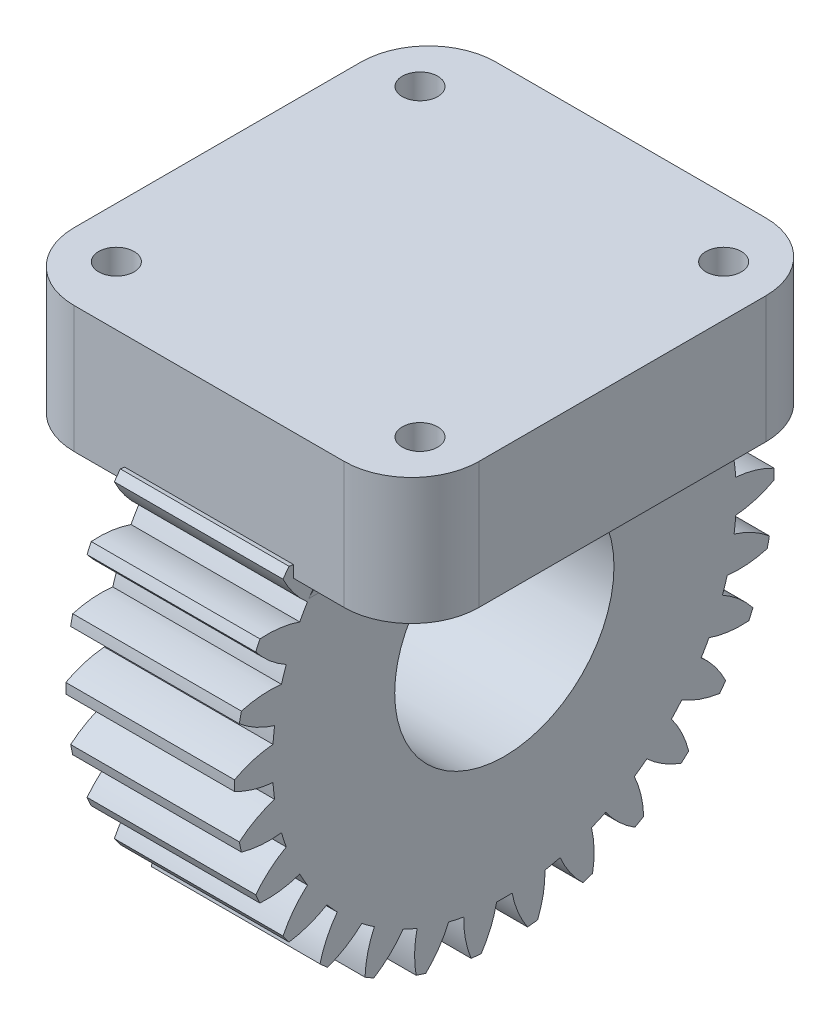
SolidWorks part; units mm, degrees
ref_plane "Front Plane" through (0, 0, 0) normal (0, 0, 1) x (1, 0, 0)
ref_plane "Top Plane" through (0, 0, 0) normal (0, 1, 0) x (1, 0, 0)
ref_plane "Right Plane" through (0, 0, 0) normal (1, 0, 0) x (0, 0, -1)
ref_plane "Plane1" through (30.4852, 0, 0) normal (1, 0, 0) x (0, 0, -1)
sketch "Sketch1" plane through (30.4852, 0, 0) normal (1, 0, 0) x (0, 0, -1)
  circle A0 centre (-23.9245, -5.8647) radius 13
  arc A1 (-55.9188, -6.4669) -> (-51.3536, -7.824) centre (-50.2847, 4.1283) ccw
  arc A2 (-51.3536, -7.824) -> (-51.1616, -9.6511) centre (-23.9245, -5.8647) ccw
  arc A3 (-51.1616, -9.6511) -> (-55.3448, -11.9278) centre (-47.631, -21.1199) ccw
  arc A4 (-55.3448, -11.9278) -> (-55.0945, -13.1057) centre (-23.9245, -5.8647) ccw
  arc A5 (-55.0945, -13.1057) -> (-50.3468, -13.4841) centre (-51.7863, -1.5707) ccw
  arc A6 (-50.3468, -13.4841) -> (-49.7791, -15.2312) centre (-23.9245, -5.8647) ccw
  arc A7 (-49.7791, -15.2312) -> (-53.3977, -18.3279) centre (-43.9412, -25.7154) ccw
  arc A8 (-53.3977, -18.3279) -> (-52.9079, -19.4281) centre (-23.9245, -5.8647) ccw
  arc A9 (-52.9079, -19.4281) -> (-48.1853, -18.8111) centre (-52.0702, -7.4573) ccw
  arc A10 (-48.1853, -18.8111) -> (-47.2667, -20.402) centre (-23.9245, -5.8647) ccw
  arc A11 (-47.2667, -20.402) -> (-50.1624, -24.1834) centre (-39.3766, -29.4434) ccw
  arc A12 (-50.1624, -24.1834) -> (-49.4545, -25.1577) centre (-23.9245, -5.8647) ccw
  arc A13 (-49.4545, -25.1577) -> (-44.9634, -23.5723) centre (-51.1241, -13.2744) ccw
  arc A14 (-44.9634, -23.5723) -> (-43.7342, -24.9375) centre (-23.9245, -5.8647) ccw
  arc A15 (-43.7342, -24.9375) -> (-45.7803, -29.2383) centre (-34.1367, -32.1408) ccw
  arc A16 (-45.7803, -29.2383) -> (-44.8854, -30.0441) centre (-23.9245, -5.8647) ccw
  arc A17 (-44.8854, -30.0441) -> (-40.8221, -27.5596) centre (-48.9891, -18.7676) ccw
  arc A18 (-40.8221, -27.5596) -> (-39.3358, -28.6394) centre (-23.9245, -5.8647) ccw
  arc A19 (-39.3358, -28.6394) -> (-40.4431, -33.2716) centre (-28.4504, -33.6898) ccw
  arc A20 (-40.4431, -33.2716) -> (-39.4002, -33.8737) centre (-23.9245, -5.8647) ccw
  arc A21 (-39.4002, -33.8737) -> (-35.9422, -30.5987) centre (-45.7588, -23.6968) ccw
  arc A22 (-35.9422, -30.5987) -> (-34.264, -31.3459) centre (-23.9245, -5.8647) ccw
  arc A23 (-34.264, -31.3459) -> (-34.3839, -36.1071) centre (-22.5663, -34.0228) ccw
  arc A24 (-34.3839, -36.1071) -> (-33.2386, -36.4792) centre (-23.9245, -5.8647) ccw
  arc A25 (-33.2386, -36.4792) -> (-30.5371, -32.5568) centre (-41.5741, -27.8468) ccw
  arc A26 (-30.5371, -32.5568) -> (-28.7402, -32.9388) centre (-23.9245, -5.8647) ccw
  arc A27 (-28.7402, -32.9388) -> (-27.8676, -37.6209) centre (-16.7416, -33.1251) ccw
  arc A28 (-27.8676, -37.6209) -> (-26.67, -37.7467) centre (-23.9245, -5.8647) ccw
  arc A29 (-26.67, -37.7467) -> (-24.843, -33.3484) centre (-36.6181, -31.036) ccw
  arc A30 (-24.843, -33.3484) -> (-23.0059, -33.3484) centre (-23.9245, -5.8647) ccw
  arc A31 (-23.0059, -33.3484) -> (-21.179, -37.7467) centre (-11.2308, -31.036) ccw
  arc A32 (-21.179, -37.7467) -> (-19.9813, -37.6209) centre (-23.9245, -5.8647) ccw
  arc A33 (-19.9813, -37.6209) -> (-19.1088, -32.9388) centre (-31.1073, -33.1251) ccw
  arc A34 (-19.1088, -32.9388) -> (-17.3118, -32.5568) centre (-23.9245, -5.8647) ccw
  arc A35 (-17.3118, -32.5568) -> (-14.6103, -36.4792) centre (-6.2748, -27.8468) ccw
  arc A36 (-14.6103, -36.4792) -> (-13.465, -36.1071) centre (-23.9245, -5.8647) ccw
  arc A37 (-13.465, -36.1071) -> (-13.585, -31.3459) centre (-25.2826, -34.0228) ccw
  arc A38 (-13.585, -31.3459) -> (-11.9067, -30.5987) centre (-23.9245, -5.8647) ccw
  arc A39 (-11.9067, -30.5987) -> (-8.4488, -33.8737) centre (-2.0902, -23.6968) ccw
  arc A40 (-8.4488, -33.8737) -> (-7.4059, -33.2716) centre (-23.9245, -5.8647) ccw
  arc A41 (-7.4059, -33.2716) -> (-8.5131, -28.6394) centre (-19.3986, -33.6898) ccw
  arc A42 (-8.5131, -28.6394) -> (-7.0269, -27.5596) centre (-23.9245, -5.8647) ccw
  arc A43 (-7.0269, -27.5596) -> (-2.9636, -30.0441) centre (1.1402, -18.7676) ccw
  arc A44 (-2.9636, -30.0441) -> (-2.0686, -29.2383) centre (-23.9245, -5.8647) ccw
  arc A45 (-2.0686, -29.2383) -> (-4.1148, -24.9375) centre (-13.7123, -32.1408) ccw
  arc A46 (-4.1148, -24.9375) -> (-2.8855, -23.5723) centre (-23.9245, -5.8647) ccw
  arc A47 (-2.8855, -23.5723) -> (1.6056, -25.1577) centre (3.2751, -13.2744) ccw
  arc A48 (1.6056, -25.1577) -> (2.3134, -24.1834) centre (-23.9245, -5.8647) ccw
  arc A49 (2.3134, -24.1834) -> (-0.5822, -20.402) centre (-8.4724, -29.4434) ccw
  arc A50 (-0.5822, -20.402) -> (0.3363, -18.8111) centre (-23.9245, -5.8647) ccw
  arc A51 (0.3363, -18.8111) -> (5.0589, -19.4281) centre (4.2213, -7.4573) ccw
  arc A52 (5.0589, -19.4281) -> (5.5487, -18.3279) centre (-23.9245, -5.8647) ccw
  arc A53 (5.5487, -18.3279) -> (1.9302, -15.2312) centre (-3.9078, -25.7154) ccw
  arc A54 (1.9302, -15.2312) -> (2.4979, -13.4841) centre (-23.9245, -5.8647) ccw
  arc A55 (2.4979, -13.4841) -> (7.2455, -13.1057) centre (3.9373, -1.5707) ccw
  arc A56 (7.2455, -13.1057) -> (7.4959, -11.9278) centre (-23.9245, -5.8647) ccw
  arc A57 (7.4959, -11.9278) -> (3.3126, -9.6511) centre (-0.218, -21.1199) ccw
  arc A58 (3.3126, -9.6511) -> (3.5046, -7.824) centre (-23.9245, -5.8647) ccw
  arc A59 (3.5046, -7.824) -> (8.0699, -6.4669) centre (2.4357, 4.1283) ccw
  arc A60 (8.0699, -6.4669) -> (8.0699, -5.2626) centre (-23.9245, -5.8647) ccw
  arc A61 (8.0699, -5.2626) -> (3.5046, -3.9054) centre (2.4357, -15.8577) ccw
  arc A62 (3.5046, -3.9054) -> (3.3126, -2.0784) centre (-23.9245, -5.8647) ccw
  arc A63 (3.3126, -2.0784) -> (7.4959, 0.1983) centre (-0.218, 9.3905) ccw
  arc A64 (7.4959, 0.1983) -> (7.2455, 1.3762) centre (-23.9245, -5.8647) ccw
  arc A65 (7.2455, 1.3762) -> (2.4979, 1.7546) centre (3.9373, -10.1588) ccw
  arc A66 (2.4979, 1.7546) -> (1.9302, 3.5018) centre (-23.9245, -5.8647) ccw
  arc A67 (1.9302, 3.5018) -> (5.5487, 6.5985) centre (-3.9078, 13.986) ccw
  arc A68 (5.5487, 6.5985) -> (5.0589, 7.6986) centre (-23.9245, -5.8647) ccw
  arc A69 (5.0589, 7.6986) -> (0.3363, 7.0816) centre (4.2213, -4.2721) ccw
  arc A70 (0.3363, 7.0816) -> (-0.5822, 8.6726) centre (-23.9245, -5.8647) ccw
  arc A71 (-0.5822, 8.6726) -> (2.3134, 12.4539) centre (-8.4724, 17.7139) ccw
  arc A72 (2.3134, 12.4539) -> (1.6056, 13.4282) centre (-23.9245, -5.8647) ccw
  arc A73 (1.6056, 13.4282) -> (-2.8855, 11.8428) centre (3.2751, 1.5449) ccw
  arc A74 (-2.8855, 11.8428) -> (-4.1148, 13.208) centre (-23.9245, -5.8647) ccw
  arc A75 (-4.1148, 13.208) -> (-2.0686, 17.5088) centre (-13.7123, 20.4113) ccw
  arc A76 (-2.0686, 17.5088) -> (-2.9636, 18.3146) centre (-23.9245, -5.8647) ccw
  arc A77 (-2.9636, 18.3146) -> (-7.0269, 15.8301) centre (1.1402, 7.0381) ccw
  arc A78 (-7.0269, 15.8301) -> (-8.5131, 16.9099) centre (-23.9245, -5.8647) ccw
  arc A79 (-8.5131, 16.9099) -> (-7.4059, 21.5421) centre (-19.3986, 21.9604) ccw
  arc A80 (-7.4059, 21.5421) -> (-8.4488, 22.1442) centre (-23.9245, -5.8647) ccw
  arc A81 (-8.4488, 22.1442) -> (-11.9067, 18.8692) centre (-2.0902, 11.9674) ccw
  arc A82 (-11.9067, 18.8692) -> (-13.585, 19.6164) centre (-23.9245, -5.8647) ccw
  arc A83 (-13.585, 19.6164) -> (-13.465, 24.3776) centre (-25.2826, 22.2933) ccw
  arc A84 (-13.465, 24.3776) -> (-14.6103, 24.7498) centre (-23.9245, -5.8647) ccw
  arc A85 (-14.6103, 24.7498) -> (-17.3118, 20.8274) centre (-6.2748, 16.1173) ccw
  arc A86 (-17.3118, 20.8274) -> (-19.1088, 21.2093) centre (-23.9245, -5.8647) ccw
  arc A87 (-19.1088, 21.2093) -> (-19.9813, 25.8914) centre (-31.1073, 21.3956) ccw
  arc A88 (-19.9813, 25.8914) -> (-21.179, 26.0173) centre (-23.9245, -5.8647) ccw
  arc A89 (-21.179, 26.0173) -> (-23.0059, 21.6189) centre (-11.2308, 19.3065) ccw
  arc A90 (-23.0059, 21.6189) -> (-24.843, 21.6189) centre (-23.9245, -5.8647) ccw
  arc A91 (-24.843, 21.6189) -> (-26.67, 26.0173) centre (-36.6181, 19.3065) ccw
  arc A92 (-26.67, 26.0173) -> (-27.8676, 25.8914) centre (-23.9245, -5.8647) ccw
  arc A93 (-27.8676, 25.8914) -> (-28.7402, 21.2093) centre (-16.7416, 21.3956) ccw
  arc A94 (-28.7402, 21.2093) -> (-30.5371, 20.8274) centre (-23.9245, -5.8647) ccw
  arc A95 (-30.5371, 20.8274) -> (-33.2386, 24.7498) centre (-41.5741, 16.1173) ccw
  arc A96 (-33.2386, 24.7498) -> (-34.3839, 24.3776) centre (-23.9245, -5.8647) ccw
  arc A97 (-34.3839, 24.3776) -> (-34.264, 19.6164) centre (-22.5663, 22.2933) ccw
  arc A98 (-34.264, 19.6164) -> (-35.9422, 18.8692) centre (-23.9245, -5.8647) ccw
  arc A99 (-35.9422, 18.8692) -> (-39.4002, 22.1442) centre (-45.7588, 11.9674) ccw
  arc A100 (-39.4002, 22.1442) -> (-40.4431, 21.5421) centre (-23.9245, -5.8647) ccw
  arc A101 (-40.4431, 21.5421) -> (-39.3358, 16.9099) centre (-28.4504, 21.9604) ccw
  arc A102 (-39.3358, 16.9099) -> (-40.8221, 15.8301) centre (-23.9245, -5.8647) ccw
  arc A103 (-40.8221, 15.8301) -> (-44.8854, 18.3146) centre (-48.9891, 7.0381) ccw
  arc A104 (-44.8854, 18.3146) -> (-45.7803, 17.5088) centre (-23.9245, -5.8647) ccw
  arc A105 (-45.7803, 17.5088) -> (-43.7342, 13.208) centre (-34.1367, 20.4113) ccw
  arc A106 (-43.7342, 13.208) -> (-44.9634, 11.8428) centre (-23.9245, -5.8647) ccw
  arc A107 (-44.9634, 11.8428) -> (-49.4545, 13.4282) centre (-51.1241, 1.5449) ccw
  arc A108 (-49.4545, 13.4282) -> (-50.1624, 12.4539) centre (-23.9245, -5.8647) ccw
  arc A109 (-50.1624, 12.4539) -> (-47.2667, 8.6726) centre (-39.3766, 17.7139) ccw
  arc A110 (-47.2667, 8.6726) -> (-48.1853, 7.0816) centre (-23.9245, -5.8647) ccw
  arc A111 (-48.1853, 7.0816) -> (-52.9079, 7.6986) centre (-52.0702, -4.2721) ccw
  arc A112 (-52.9079, 7.6986) -> (-53.3977, 6.5985) centre (-23.9245, -5.8647) ccw
  arc A113 (-53.3977, 6.5985) -> (-49.7791, 3.5018) centre (-43.9412, 13.986) ccw
  arc A114 (-49.7791, 3.5018) -> (-50.3468, 1.7546) centre (-23.9245, -5.8647) ccw
  arc A115 (-50.3468, 1.7546) -> (-55.0945, 1.3762) centre (-51.7863, -10.1588) ccw
  arc A116 (-55.0945, 1.3762) -> (-55.3448, 0.1983) centre (-23.9245, -5.8647) ccw
  arc A117 (-55.3448, 0.1983) -> (-51.1616, -2.0784) centre (-47.631, 9.3905) ccw
  arc A118 (-51.1616, -2.0784) -> (-51.3536, -3.9054) centre (-23.9245, -5.8647) ccw
  arc A119 (-51.3536, -3.9054) -> (-55.9188, -5.2626) centre (-50.2847, -15.8577) ccw
  arc A120 (-55.9188, -5.2626) -> (-55.9188, -6.4669) centre (-23.9245, -5.8647) ccw
extrude "Boss-Extrude1" add sketch "Sketch1" against normal blind 20
sketch "Sketch3" plane through (30.4852, 0, 0) normal (1, 0, 0) x (0, 0, -1)
  line L1 (-48.9245, 11.9354) -> (1.0755, 11.9354)
  line L2 (-48.9245, 11.9354) -> (-48.9245, 26.9354)
  line L3 (-48.9245, 26.9354) -> (1.0755, 26.9354)
  line L4 (1.0755, 11.9354) -> (1.0755, 26.9354)
  dimension "D1" = 50
  dimension "D2" = 15
extrude "Boss-Extrude2" add sketch "Sketch3" along normal blind 14 and the other way blind 34
fillet "Fillet1" radius 3 2 edges at (10.4852, 11.9354, 23.9245) (30.4852, 11.9354, 23.9245)
sketch "Sketch4" plane through (0, 26.9354, 0) normal (0, 1, 0) x (1, 0, 0)
  circle A0 centre (2.4852, -5.9245) radius 2.1
  circle A1 centre (38.4852, -5.9245) radius 2.1
  circle A2 centre (38.4852, -41.9245) radius 2.1
  circle A3 centre (2.4852, -41.9245) radius 2.1
  point P6 (20.4852, -23.9245)
  dimension "D3" = 4.2
  dimension "D4" = 4.2
  dimension "D5" = 4.2
  dimension "D6" = 4.2
  dimension "D1" = 36
  dimension "D2" = 36
extrude "Cut-Extrude3" cut sketch "Sketch4" against normal blind 84
fillet "Fillet2" radius 8 4 edges at (-3.5148, 19.4354, 48.9245) (44.4852, 19.4354, 48.9245) (44.4852, 19.4354, -1.0755) (-3.5148, 19.4354, -1.0755)
